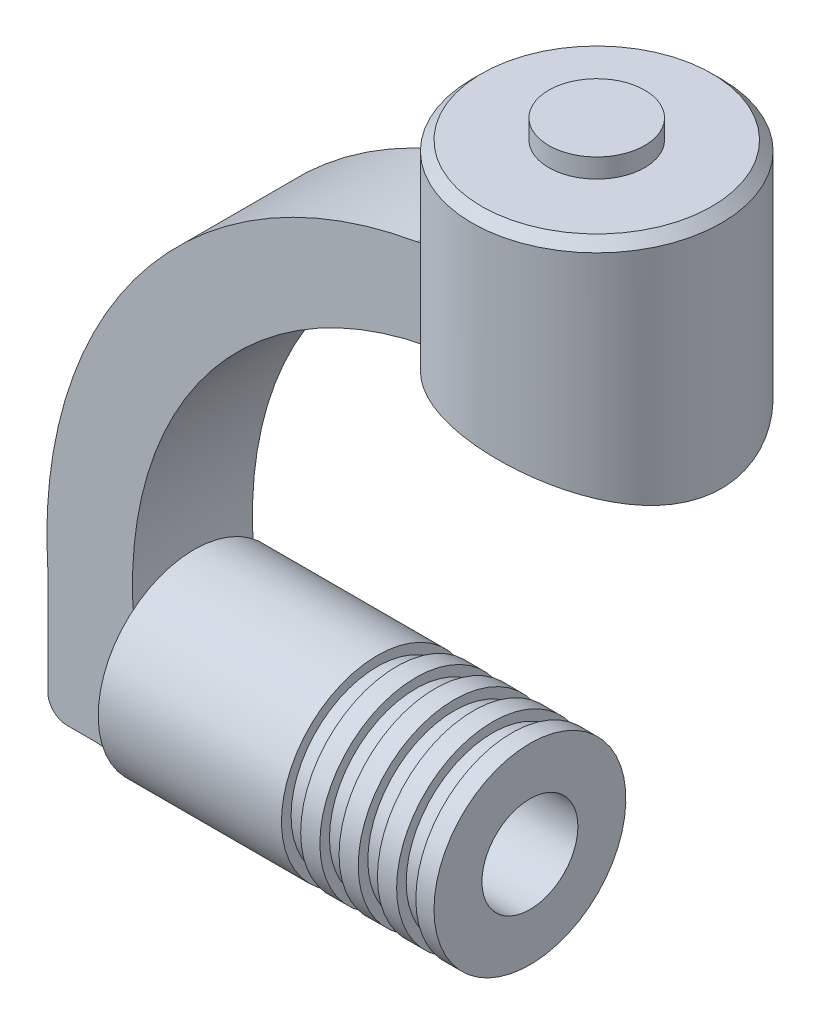
SolidWorks part; units mm, degrees
ref_plane "Ön Düzlem" through (0, 0, 0) normal (0, 0, 1) x (1, 0, 0)
ref_plane "Üst Düzlem" through (0, 0, 0) normal (0, 1, 0) x (1, 0, 0)
ref_plane "Sağ Düzlem" through (0, 0, 0) normal (1, 0, 0) x (0, 0, -1)
sketch "Sketch1" plane through (0, 0, 0) normal (0, 0, 1) x (1, 0, 0)
  line L0 (-90, 0) -> (0, 0) construction
  line L1 (0, 0) -> (0, 120) construction
  line L2 (-90, 12.5) -> (-90, -12.5)
  line L3 (-90, -12.5) -> (-108, -12.5)
  line L4 (-108, -12.5) -> (-108, 13.6093)
  line L5 (0, 120) -> (-26, 120) construction
  line L6 (-26, 120) -> (-26, 94) construction
  line L7 (-26, 94) -> (-31.068, 111.2718)
  arc A0 (-90, 12.5) -> (-26, 94) centre (-15.3304, 19.7426) cw
  arc A1 (-108, 13.6093) -> (-31.068, 111.2718) centre (-15.3304, 19.7426) cw
  arc A2 (-31.068, 111.2718) -> (-26, 112) centre (-15.3304, 19.7426) cw construction
  point P6 (-90, 0)
  dimension "D5" = 75.02
  dimension "D1" = 90
  dimension "D2" = 120
  dimension "D3" = 18
  dimension "D4" = 25
  dimension "D6" = 26
  dimension "D7" = 8
  dimension "D8" = 18
  dimension "D9" = 18
extrude "Boss-Extrude1" add sketch "Sketch1" along normal blind 25
sketch "Sketch3" plane through (-90, 0, 0) normal (1, 0, 0) x (0, 0, -1)
  line L0 (-25, 0) -> (0, 0) construction
  line L1 (-25, -12.5) -> (-25, 12.5) construction
  circle A0 centre (-12.5, 0) radius 20
  dimension "D1" = 40
extrude "Boss-Extrude2" add sketch "Sketch3" along normal blind 70 contours A0
fillet "Fillet1" radius 10 1 edges at (-90, -12.5, 12.5)
fillet "Fillet2" radius 4 1 edges at (-108, -12.5, 12.5)
sketch "Sketch4" plane through (-20, 0, 0) normal (1, 0, 0) x (0, 0, -1)
  circle A0 centre (-12.5, 0) radius 10
  dimension "D1" = 20
extrude "Cut-Extrude1" cut sketch "Sketch4" against normal blind 20
sketch "Sketch5" plane through (0, 0, 0) normal (0, 0, 1) x (1, 0, 0)
  line L0 (0, 0) -> (-90, 0) construction
  line L1 (-90, -15.6125) -> (-90, 12.5) construction
  line L2 (0, 0) -> (0, 120) construction
  dimension "D1" = 120
ref_plane "Plane1" through (0, 120, 0) normal (0, 1, 0) x (1, 0, 0)
sketch "Sketch6" plane through (0, 120, 0) normal (0, 1, 0) x (1, 0, 0)
  line L0 (-31.068, -12.5) -> (18.932, -12.5) construction
  line L1 (-31.068, -25) -> (-31.068, 0) construction
  circle A0 centre (-6.068, -12.5) radius 26
  dimension "D2" = 52
  dimension "D1" = 50
extrude "Boss-Extrude3" add sketch "Sketch6" against normal up to surface (25.8114 mm away) up to face at (-66.1663, 59.6628, 12.5)
sketch "Sketch7" plane through (1.4565, 0.4274, 0) normal (0.9595, 0.2816, 0) x (0, 0, -1)
  line L2 (-25, 115.5177) -> (-25, 107.6969)
  line L3 (-19.6414, 115.5177) -> (-25, 115.5177)
  line L4 (-25, 115.5177) -> (-25, 107.6969)
  line L5 (-19.6414, 115.5177) -> (-25, 115.5177)
  ellipse E1 centre (-12.5, 26.7249) end of major axis (-12.5, 119.0694) minor radius 26 (-19.6414, 115.5177) -> (-25, 107.6969) ccw
  ellipse E2 centre (-12.5, 26.7249) end of major axis (-12.5, 119.0694) minor radius 26 (-19.6414, 115.5177) -> (-25, 107.6969) ccw
  dimension "D1" = 0
extrude "Boss-Extrude4" add sketch "Sketch7" along normal up to surface up to face at (-6.068, 120, 38.5)
sketch "Sketch8" plane through (1.4565, 0.4274, 0) normal (0.9595, 0.2816, 0) x (0, 0, -1)
  line L2 (0, 115.5177) -> (-5.3586, 115.5177)
  line L3 (0, 107.6969) -> (0, 115.5177)
  line L4 (0, 115.5177) -> (-5.3586, 115.5177)
  line L5 (0, 107.6969) -> (0, 115.5177)
  ellipse E1 centre (-12.5, 26.7249) end of major axis (-12.5, 119.0694) minor radius 26 (0, 107.6969) -> (-5.3586, 115.5177) ccw
  ellipse E2 centre (-12.5, 26.7249) end of major axis (-12.5, 119.0694) minor radius 26 (0, 107.6969) -> (-5.3586, 115.5177) ccw
  dimension "D1" = 0
extrude "Boss-Extrude5" add sketch "Sketch8" along normal up to surface up to face at (-6.068, 120, 38.5)
sketch "Sketch11" plane through (0, 0, 0) normal (0, 1, 0) x (1, 0, 0)
  line L0 (-20, 7.5) -> (-90, 7.5) construction
  line L1 (-23.79, 9.5) -> (-27.79, 9.5)
  line L2 (-23.79, 9.5) -> (-23.79, 5.5)
  line L3 (-23.79, 5.5) -> (-27.79, 5.5)
  line L4 (-27.79, 9.5) -> (-27.79, 5.5)
  line L5 (-23.79, 9.5) -> (-27.79, 5.5) construction
  line L6 (-23.79, 5.5) -> (-27.79, 9.5) construction
  line L7 (-90, -12.5) -> (-20, -12.5) construction
  line L8 (-31.79, 9.5) -> (-35.79, 9.5)
  line L9 (-31.79, 9.5) -> (-31.79, 5.5)
  line L10 (-31.79, 5.5) -> (-35.79, 5.5)
  line L11 (-35.79, 9.5) -> (-35.79, 5.5)
  line L12 (-31.79, 9.5) -> (-35.79, 5.5) construction
  line L13 (-31.79, 5.5) -> (-35.79, 9.5) construction
  line L14 (-39.79, 9.5) -> (-43.79, 9.5)
  line L15 (-39.79, 9.5) -> (-39.79, 5.5)
  line L16 (-39.79, 5.5) -> (-43.79, 5.5)
  line L17 (-43.79, 9.5) -> (-43.79, 5.5)
  line L18 (-39.79, 9.5) -> (-43.79, 5.5) construction
  line L19 (-39.79, 5.5) -> (-43.79, 9.5) construction
  line L20 (-47.79, 9.5) -> (-51.79, 9.5)
  line L21 (-47.79, 9.5) -> (-47.79, 5.5)
  line L22 (-47.79, 5.5) -> (-51.79, 5.5)
  line L23 (-51.79, 9.5) -> (-51.79, 5.5)
  line L24 (-47.79, 9.5) -> (-51.79, 5.5) construction
  line L25 (-47.79, 5.5) -> (-51.79, 9.5) construction
  line L26 (-90, -25) -> (-90, 0) construction
  line L27 (-20, 7.5) -> (-20, -12.5) construction
  point P0 (-25.79, 7.5)
  point P7 (-33.79, 7.5)
  point P12 (-41.79, 7.5)
  point P17 (-49.79, 7.5)
  dimension "D1" = 4
  dimension "D2" = 4
  dimension "D3" = 4
  dimension "D4" = 4
  dimension "D5" = 4
  dimension "D6" = 4
  dimension "D7" = 4
  dimension "D8" = 4
  dimension "D9" = 3.79
revolve "Cut-Revolve1" cut sketch "Sketch11" angle 360 about L7
sketch "Sketch12" plane through (0, 120, 0) normal (0, 1, 0) x (1, 0, 0)
  circle A1 centre (-6.068, -12.5) radius 26
  circle A2 centre (-6.068, -12.5) radius 26
  dimension "D1" = 0
extrude "Boss-Extrude6" add sketch "Sketch12" along normal blind 15.9
sketch "Sketch13" plane through (0, 135.9, 0) normal (0, 1, 0) x (1, 0, 0)
  circle A0 centre (-6.068, -12.5) radius 10
  dimension "D1" = 20
extrude "Boss-Extrude7" add sketch "Sketch13" along normal blind 4
chamfer "Chamfer1" distance 2 angle 45 1 edges at (-6.068, 135.9, 38.5)
